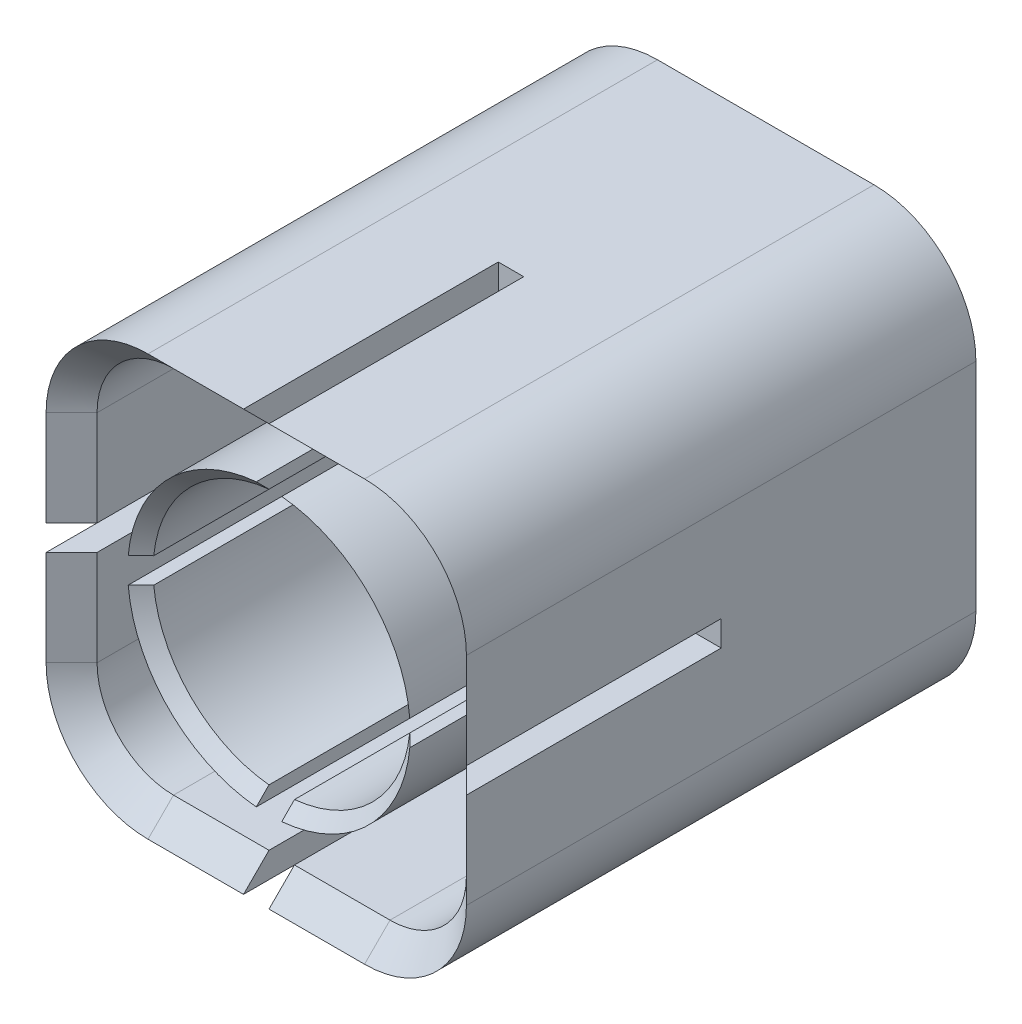
SolidWorks part; units mm, degrees
ref_plane "Front Plane" through (0, 0, 0) normal (0, 0, 1) x (1, 0, 0)
ref_plane "Top Plane" through (0, 0, 0) normal (0, 1, 0) x (1, 0, 0)
ref_plane "Right Plane" through (0, 0, 0) normal (1, 0, 0) x (0, 0, -1)
sketch "Sketch2" plane through (0, 0, 0) normal (0, 0, 1) x (1, 0, 0)
  line L1 (4.25, -8.25) -> (-4.25, -8.25)
  line L2 (8.25, -4.25) -> (8.25, 4.25)
  line L3 (4.25, 8.25) -> (-4.25, 8.25)
  line L4 (-8.25, -4.25) -> (-8.25, 4.25)
  line L5 (8.25, -8.25) -> (-8.25, 8.25) construction
  line L6 (8.25, 8.25) -> (-8.25, -8.25) construction
  arc A0 (-8.25, -4.25) -> (-4.25, -8.25) centre (-4.25, -4.25) ccw
  arc A1 (8.25, -4.25) -> (4.25, -8.25) centre (4.25, -4.25) cw
  arc A2 (4.25, 8.25) -> (8.25, 4.25) centre (4.25, 4.25) cw
  arc A3 (-4.25, 8.25) -> (-8.25, 4.25) centre (-4.25, 4.25) ccw
  point P0 (0, 0)
  point P6 (8.0313, 7.9687)
  point P7 (-7.7435, -8.0177)
  point P8 (0, 0)
  point P9 (-7.8386, -8.1892)
  point P10 (7.9057, -7.8669)
  point P11 (0, 0)
  point P12 (-7.9798, 7.9798)
  point P13 (7.9156, -7.8472)
  point P14 (-7.9867, -7.9867)
  point P16 (-7.9859, 8.0141)
  point P17 (0, 0)
  point P18 (7.9406, 7.9585)
  point P19 (7.9972, 8.0028)
  point P20 (-8.0047, 7.9695)
  dimension "D3" = 4
  dimension "D1" = 16.5
  dimension "D2" = 16.5
extrude "Boss-Extrude1" add sketch "Sketch2" along normal mid plane 20 contours L3 A3 L4 A0 L1 A1 L2 A2
shell "Shell7" thickness 1 removed face at (0, 0, 10)
sketch "Sketch4" plane through (0, 0, -9) normal (0, 0, 1) x (1, 0, 0)
  circle A0 centre (0, 0) radius 5.05
  circle A1 centre (0, 0) radius 5.55
  dimension "D1" = 10.1
  dimension "D2" = 11.1
extrude "Boss-Extrude2" add sketch "Sketch4" along normal up to surface (19 mm away) separate body up to face at (0, 0, 10)
chamfer "Chamfer2" distance 1 angle 45 1 edges at (-5.05, 0, 10)
chamfer "Chamfer4" distance 1 angle 45 8 edges at (6.3713, -6.3713, 10) (7.25, 0, 10) (0, -7.25, 10) (6.3713, 6.3713, 10) (-6.3713, -6.3713, 10) (0, 7.25, 10) (-7.25, 0, 10) (-6.3713, 6.3713, 10)
sketch "Sketch10" plane through (0, 0, 0) normal (0, 0, 1) x (1, 0, 0)
  line L0 (0, 0) -> (0, 8.5657) construction
  line L1 (0, 0) -> (11.9886, 0) construction
  line L2 (0, 0) -> (10.1142, 10.1142) construction
  line L3 (0.5, 3) -> (-0.5, 3)
  line L4 (0.5, 3) -> (0.5, 13)
  line L5 (0.5, 13) -> (-0.5, 13)
  line L6 (-0.5, 3) -> (-0.5, 13)
  line L7 (0.5, 3) -> (-0.5, 13) construction
  line L8 (0.5, 13) -> (-0.5, 3) construction
  line L9 (3, -0.5) -> (13, -0.5)
  line L10 (3, 0.5) -> (3, -0.5)
  line L11 (3, 0.5) -> (13, 0.5)
  line L12 (13, 0.5) -> (13, -0.5)
  line L13 (0.5, -3) -> (-0.5, -3)
  line L14 (0.5, -3) -> (0.5, -13)
  line L15 (-0.5, -3) -> (-0.5, -13)
  line L16 (0.5, -13) -> (-0.5, -13)
  line L17 (-3, 0.5) -> (-3, -0.5)
  line L18 (-3, -0.5) -> (-13, -0.5)
  line L19 (-13, 0.5) -> (-13, -0.5)
  line L20 (-3, 0.5) -> (-13, 0.5)
  point P3 (0, 8)
  dimension "D1" = 1
  dimension "D2" = 10
  dimension "D3" = 8
  dimension "D4" = 45
extrude "Cut-Extrude2" cut sketch "Sketch10" along normal blind 10
